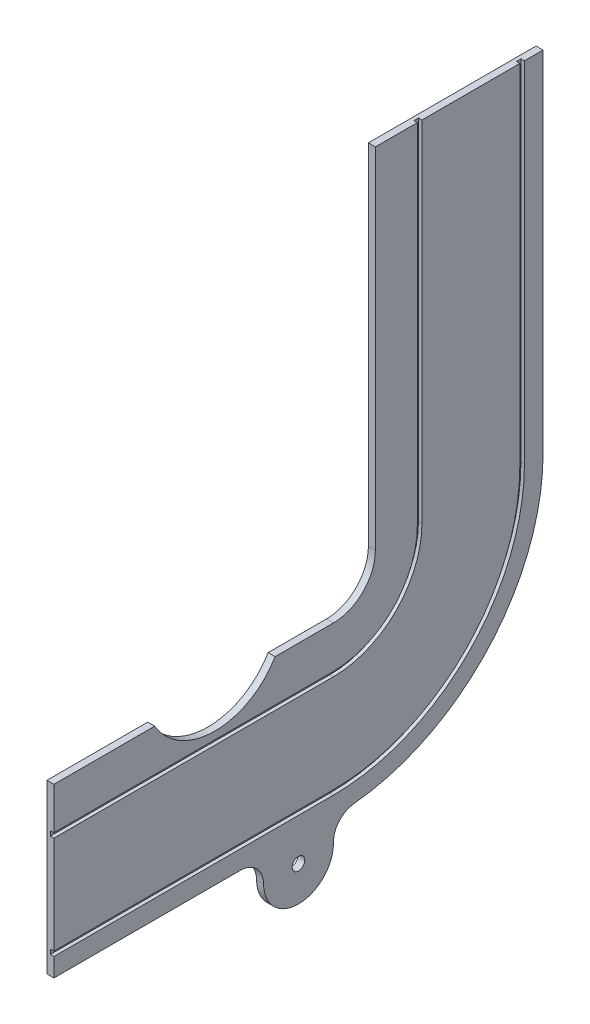
SolidWorks part; units mm, degrees
ref_plane "Front Plane" through (0, 0, 0) normal (0, 0, 1) x (1, 0, 0)
ref_plane "Top Plane" through (0, 0, 0) normal (0, 1, 0) x (1, 0, 0)
ref_plane "Right Plane" through (0, 0, 0) normal (1, 0, 0) x (0, 0, -1)
sketch "Sketch1" plane through (0, 0, 0) normal (1, 0, 0) x (0, 0, -1)
  line L0 (90, 0) -> (0, 0) construction
  line L1 (0, 0) -> (0, -90) construction
  line L2 (0, -18) -> (-120, -18)
  line L3 (-120, -18) -> (-120, -90)
  line L4 (-120, -90) -> (0, -90)
  line L5 (18, 0) -> (18, 150)
  line L6 (18, 150) -> (90, 150)
  line L7 (90, 150) -> (90, 0)
  arc A0 (0, -90) -> (90, 0) centre (0, 0) ccw
  arc A1 (0, -18) -> (18, 0) centre (0, 0) ccw
  dimension "D1" = 180
  dimension "D2" = 72
  dimension "D3" = 120
  dimension "D4" = 150
extrude "Boss-Extrude1" add sketch "Sketch1" along normal blind 3
sketch "Sketch2" plane through (3, 0, 0) normal (1, 0, 0) x (0, 0, -1)
  line L0 (0, 0) -> (90, 0) construction
  line L1 (0, 0) -> (0, -90) construction
  line L2 (0, -38) -> (-120, -38)
  line L3 (-120, -18) -> (-120, -90) construction
  line L4 (0, -80) -> (-120, -80)
  line L5 (38, 0) -> (38, 150)
  line L6 (90, 150) -> (18, 150) construction
  line L7 (80, 0) -> (80, 150)
  line L8 (36, 0) -> (36, 150)
  line L9 (0, -36) -> (-120, -36)
  line L10 (0, -82) -> (-120, -82)
  line L11 (82, 0) -> (82, 150)
  line L12 (36, 150) -> (38, 150)
  line L13 (80, 150) -> (82, 150)
  line L14 (-120, -80) -> (-120, -82)
  line L15 (-120, -36) -> (-120, -38)
  arc A0 (0, -38) -> (38, 0) centre (0, 0) ccw
  arc A1 (0, -80) -> (80, 0) centre (0, 0) ccw
  arc A2 (0, -36) -> (36, 0) centre (0, 0) ccw
  arc A3 (0, -82) -> (82, 0) centre (0, 0) ccw
  dimension "D1" = 42
  dimension "D2" = 80
  dimension "D3" = 2
  dimension "D4" = 2
extrude "Cut-Extrude1" cut sketch "Sketch2" against normal blind 1.5
sketch "Sketch3" plane through (3, 0, 0) normal (1, 0, 0) x (0, 0, -1)
  line L0 (-120, -90) -> (0, -90) construction
  line L2 (-30, -100) -> (0, -100)
  line L3 (-30, -100) -> (-30, -90)
  line L4 (-30, -90) -> (0, -90)
  line L5 (0, -100) -> (0, -90)
  circle A0 centre (-15, -100) radius 15
  line M5 (-120, -90) -> (0, -90)
  dimension "D1" = 30
  dimension "D3" = 10
  dimension "D2" = 15
extrude "Boss-Extrude2" add sketch "Sketch3" against normal blind 3 contours A0 L3 M5 | L2 A0 L4 | A0 L5 M5 | L2 A0 region at (3, -95.2234, 15) region at (3, -106.3662, 15) region at (3, -92.4319, 28.8843) region at (3, -92.4319, 1.1157)
fillet "Fillet1" radius 10 2 edges at (1.5, -90, 0) (1.5, -90, 30)
sketch "Sketch4" plane through (3, 0, 0) normal (1, 0, 0) x (0, 0, -1)
  circle A0 centre (-15, -100) radius 2.7
  dimension "D1" = 5.4
extrude "Cut-Extrude2" cut sketch "Sketch4" against normal through all
sketch "Sketch5" plane through (3, 0, 0) normal (1, 0, 0) x (0, 0, -1)
  line L0 (-51, -36) -> (-51, 29.6868) construction
  line L1 (0, -36) -> (-120, -36) construction
  circle A0 centre (-50.8809, -2.772) radius 30
  dimension "D2" = 60
  dimension "D1" = 51
extrude "Cut-Extrude3" cut sketch "Sketch5" against normal through all
